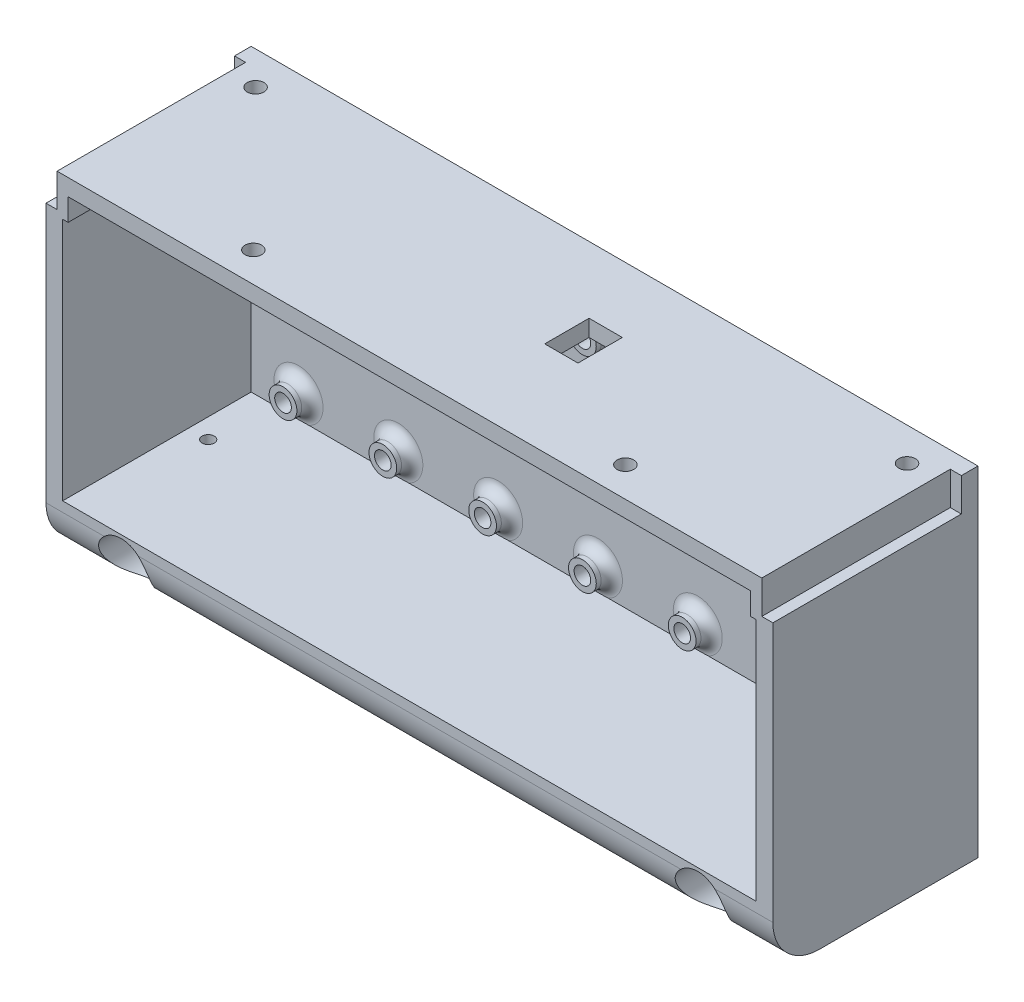
SolidWorks part; units mm, degrees
material "ABS"
ref_plane "Alzado" through (0, 0, 0) normal (0, 0, 1) x (1, 0, 0)
ref_plane "Planta" through (0, 0, 0) normal (0, 1, 0) x (1, 0, 0)
ref_plane "Vista lateral" through (0, 0, 0) normal (1, 0, 0) x (0, 0, -1)
sketch "Croquis2" plane through (0, 0, 0) normal (0, 0, 1) x (1, 0, 0)
  line L0 (0, 0) -> (131.1, 0)
  line L1 (131.1, 0) -> (131.1, -54)
  line L2 (131.1, -54) -> (0, -54)
  line L3 (0, -54) -> (0, 0)
  dimension "D1" = 131.1
  dimension "D2" = 54
extrude "Saliente-Extruir2" add sketch "Croquis2" along normal blind 3
sketch "Croquis3" plane through (0, 0, 3) normal (0, 0, 1) x (1, 0, 0)
  line L0 (0, -6) -> (2, -6)
  line L1 (0, 0) -> (0, -54) construction
  line L2 (2, -6) -> (2, 0)
  line L3 (131.1, 0) -> (0, 0) construction
  line L4 (2, 0) -> (129.1, 0)
  line L5 (129.1, 0) -> (129.1, -6)
  line L6 (129.1, -6) -> (131.1, -6)
  line L7 (131.1, -54) -> (131.1, 0) construction
  line L8 (131.1, -6) -> (131.1, -54)
  line L9 (131.1, -54) -> (0, -54)
  line L10 (0, -54) -> (0, -6)
  line L11 (65.55, 0) -> (66.55, 0)
  line L12 (65.55, 0) -> (64.55, 0)
  line L13 (64.55, 0) -> (64.55, -6)
  line L14 (66.55, 0) -> (66.55, -6)
  line L15 (64.55, -6) -> (62.55, -6)
  line L16 (62.55, -6) -> (62.55, 0)
  line L17 (66.55, -6) -> (68.55, -6)
  line L18 (68.55, -6) -> (68.55, 0)
  line L19 (3, -7) -> (128.1, -7)
  line L20 (128.1, -7) -> (128.1, -51)
  line L21 (128.1, -51) -> (3, -51)
  line L22 (3, -51) -> (3, -7)
  line L23 (62.55, 0) -> (64.55, 0)
  line L24 (66.55, 0) -> (68.55, 0)
  point P31 (130.1, -6)
  line M15 (0, 0) -> (0, -54)
  line M16 (0, -54) -> (131.1, -54)
  line M17 (131.1, -54) -> (131.1, 0)
  line M18 (131.1, 0) -> (0, 0)
  dimension "D1" = 2
  dimension "D2" = 2
  dimension "D3" = 6
  dimension "D4" = 2
  dimension "D5" = 2
  dimension "D6" = 1
  dimension "D7" = 1
  dimension "D8" = 3
  dimension "D9" = 3
  dimension "D10" = 3
  dimension "D11" = 1
extrude "Saliente-Extruir3" add sketch "Croquis3" along normal blind 34 contours L18 L17 L14 L4 L13 L15 L16 L2 L0 L6 L5 L21 L22 L19 L20 M18 M15 M16 M17 | L16 L15 L13 L4 | L17 L18 L4 L14 region at (1, -7.4179, 3) region at (63.55, -3, 3) region at (67.55, -3, 3)
sketch "Croquis4" plane through (0, -54, 0) normal (0, -1, 0) x (1, 0, 0)
  line L4 (0, 0) -> (131.1, 0)
  line L5 (131.1, 0) -> (131.1, 37)
  line L6 (131.1, 37) -> (0, 37)
  line L7 (0, 37) -> (0, 0)
  line L8 (0, 0) -> (131.1, 0)
  line L9 (131.1, 0) -> (131.1, 37)
  line L10 (131.1, 37) -> (0, 37)
  line L11 (0, 37) -> (0, 0)
  dimension "D1" = 0
extrude "Saliente-Extruir4" add sketch "Croquis4" along normal blind 7.2
sketch "Croquis5" plane through (0, 0, 37) normal (0, 0, 1) x (1, 0, 0)
  line L0 (3, -7) -> (128.1, -7) construction
  line L1 (4, -7) -> (65.55, -7)
  line L2 (4, -7) -> (4, -3)
  line L3 (4, -3) -> (65.55, -3)
  line L5 (129.1, 0) -> (2, 0) construction
  line L6 (65.55, -7) -> (65.55, 0) construction
  line L7 (129.1, 0) -> (2, 0) construction
  line L8 (127.1, -3) -> (65.55, -3)
  line L11 (127.1, -7) -> (127.1, -3)
  line L12 (65.55, -7) -> (127.1, -7)
  line M24 (3, -7) -> (128.1, -7)
  dimension "D1" = 1
  dimension "D3" = 3
extrude "Cortar-Extruir1" cut sketch "Croquis5" against normal up to vertex (34 mm away) contours L6 L3 L2 M24 | L6 L11 L8 M24 region at (34.775, -5, 37) region at (96.325, -5, 37) up to point (3, -7, 3)
sketch "Croquis6" plane through (0, -3, 0) normal (0, -1, 0) x (1, 0, 0)
  line L0 (127.1, 37) -> (4, 37) construction
  line L1 (0, 37) -> (0, 3) construction
  line L2 (131.1, 37) -> (131.1, 3) construction
  line L3 (131.1, 0) -> (0, 0) construction
  line L5 (72.95, 20) -> (78.95, 20)
  line L6 (72.95, 20) -> (72.95, 12)
  line L7 (72.95, 12) -> (78.95, 12)
  line L8 (78.95, 20) -> (78.95, 12)
  line L9 (4, 3) -> (4, 37) construction
  line L10 (4, 3) -> (127.1, 3) construction
  circle A0 centre (32, 31.6) radius 1.5
  circle A1 centre (99.1, 31.6) radius 1.5
  circle A2 centre (6.8, 6) radius 1.5
  circle A3 centre (124.3, 6) radius 1.5
  dimension "D3" = 3
  dimension "D1" = 5.4
  dimension "D2" = 32
  dimension "D4" = 32
  dimension "D5" = 6.8
  dimension "D6" = 6
  dimension "D7" = 6.8
  dimension "D8" = 68.95
  dimension "D9" = 9
  dimension "D11" = 6
  dimension "D12" = 8
extrude "Cortar-Extruir2" cut sketch "Croquis6" against normal up to next
sketch "Croquis8" plane through (0, 0, 37) normal (0, 0, 1) x (1, 0, 0)
  line L0 (65.55, -61.2) -> (65.55, -51) construction
  line L1 (131.1, -61.2) -> (0, -61.2) construction
  line L2 (128.1, -51) -> (3, -51) construction
  circle A0 centre (13.55, -56.1) radius 4.5
  circle A1 centre (117.55, -56.1) radius 4.5
  point P8 (65.55, -56.1)
  dimension "D1" = 9
  dimension "D2" = 52
extrude "Cortar-Extruir3" cut sketch "Croquis8" against normal blind 33
sketch "Croquis9" plane through (0, 0, 37) normal (0, 0, 1) x (1, 0, 0)
  circle A0 centre (13.55, -56.1) radius 2.5
  circle A1 centre (117.55, -56.1) radius 2.5
  dimension "D1" = 5
extrude "Cortar-Extruir4" cut sketch "Croquis9" against normal through all
fillet "Redondeo1" radius 8.4 1 edges at (65.55, -61.2, 37)
sketch "Croquis10" plane through (0, 0, 3) normal (0, 0, 1) x (1, 0, 0)
  line L2 (4, -3) -> (127.1, -3) construction
  circle A0 centre (65.55, -10) radius 2.5
  circle A1 centre (65.55, -10) radius 1.5
  circle A2 centre (83.55, -10) radius 1.5
  circle A3 centre (83.55, -10) radius 2.5
  circle A4 centre (101.55, -10) radius 1.5
  circle A5 centre (101.55, -10) radius 2.5
  circle A6 centre (119.55, -10) radius 1.5
  circle A7 centre (119.55, -10) radius 2.5
  circle A8 centre (83.55, -47) radius 1.5
  circle A9 centre (83.55, -47) radius 2.5
  circle A10 centre (101.55, -47) radius 1.5
  circle A11 centre (101.55, -47) radius 2.5
  circle A12 centre (119.55, -47) radius 1.5
  circle A13 centre (119.55, -47) radius 2.5
  circle A16 centre (47.55, -10) radius 2.5
  circle A17 centre (47.55, -10) radius 1.5
  circle A18 centre (29.55, -10) radius 2.5
  circle A19 centre (29.55, -10) radius 1.5
  circle A20 centre (11.55, -10) radius 2.5
  circle A21 centre (11.55, -10) radius 1.5
  circle A22 centre (47.55, -47) radius 2.5
  circle A23 centre (47.55, -47) radius 1.5
  circle A24 centre (29.55, -47) radius 2.5
  circle A25 centre (29.55, -47) radius 1.5
  circle A26 centre (11.55, -47) radius 2.5
  circle A27 centre (11.55, -47) radius 1.5
  circle A28 centre (65.55, -47) radius 2.5
  circle A29 centre (65.55, -47) radius 1.5
  circle A30 centre (65.55, -47) radius 2.5 [skipped]
  circle A31 centre (65.55, -47) radius 1.5 [skipped]
  point P3 (65.55, -3)
  dimension "D1" = 5
  dimension "D3" = 3
  dimension "D2" = 7
  dimension "D4" = 4
  dimension "D5" = 2
  dimension "D6" = 4
  dimension "D7" = 2
extrude "Saliente-Extruir5" add sketch "Croquis10" along normal blind 2.8
fillet "Redondeo2" radius 1.92 14 edges at (9.05, -47, 3) (27.05, -47, 3) (45.05, -47, 3) (63.05, -47, 3) (81.05, -47, 3) (99.05, -47, 3) (117.05, -47, 3) (117.05, -10, 3) (99.05, -10, 3) (81.05, -10, 3) (63.05, -10, 3) (45.05, -10, 3) (27.05, -10, 3) (9.05, -10, 3)
sketch "Croquis11" plane through (0, -61.2, 0) normal (0, -1, 0) x (1, 0, 0)
  line L0 (0, 28.6) -> (0, 0) construction
  line L1 (0, 0) -> (131.1, 0) construction
  line L2 (65.55, 0) -> (65.55, 28.6) construction
  line L3 (131.1, 28.6) -> (0, 28.6) construction
  circle A0 centre (6.55, 14.3) radius 1.1
  circle A1 centre (124.55, 14.3) radius 1.1
  dimension "D3" = 2.2
  dimension "D1" = 6.55
  dimension "D2" = 14.3
extrude "Cortar-Extruir5" cut sketch "Croquis11" against normal up to next
